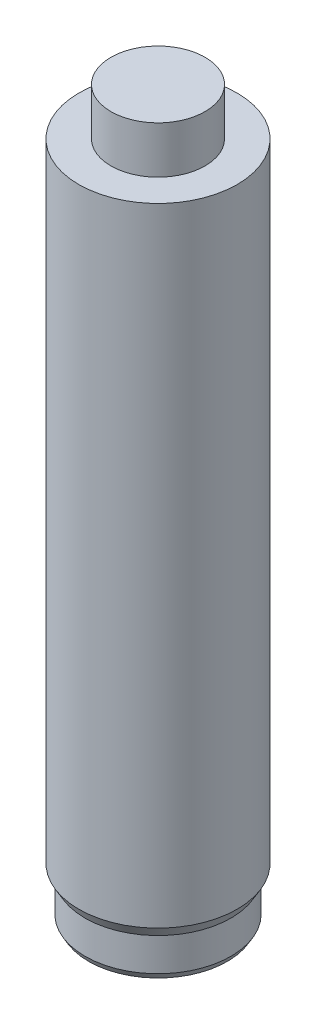
SolidWorks part; units mm, degrees
material "Chrome Stainless Steel"
ref_plane "Front Plane" through (0, 0, 0) normal (0, 0, 1) x (1, 0, 0)
ref_plane "Top Plane" through (0, 0, 0) normal (0, 1, 0) x (1, 0, 0)
ref_plane "Right Plane" through (0, 0, 0) normal (1, 0, 0) x (0, 0, -1)
sketch "Sketch1" plane through (0, 0, 0) normal (0, 1, 0) x (1, 0, 0)
  circle A0 centre (0, 0) radius 25.25
  circle A1 centre (0, 0) radius 13.45
extrude "Boss-Extrude1" add sketch "Sketch1" along normal blind 216
sketch "Sketch2" plane through (0, 0, 0) normal (0, -1, 0) x (1, 0, 0)
  circle A0 centre (0, 0) radius 23.25
extrude "Cut-Extrude1" cut sketch "Sketch2" against normal blind 12 flip side to cut
chamfer "Chamfer2" distance 4 angle 30 1 edges at (0, 12, -25.25) first distance on face at (0, 216, 25.25)
chamfer "Chamfer3" distance 2 angle 30 1 edges at (0, 0, -23.25) first distance on face at (0, 12.5359, 23.25)
sketch "Sketch3" plane through (0, 216, 0) normal (0, 1, 0) x (1, 0, 0)
  circle A0 centre (0, 0) radius 15
  dimension "D1" = 30
extrude "inside_head" add sketch "Sketch3" along normal blind 15
